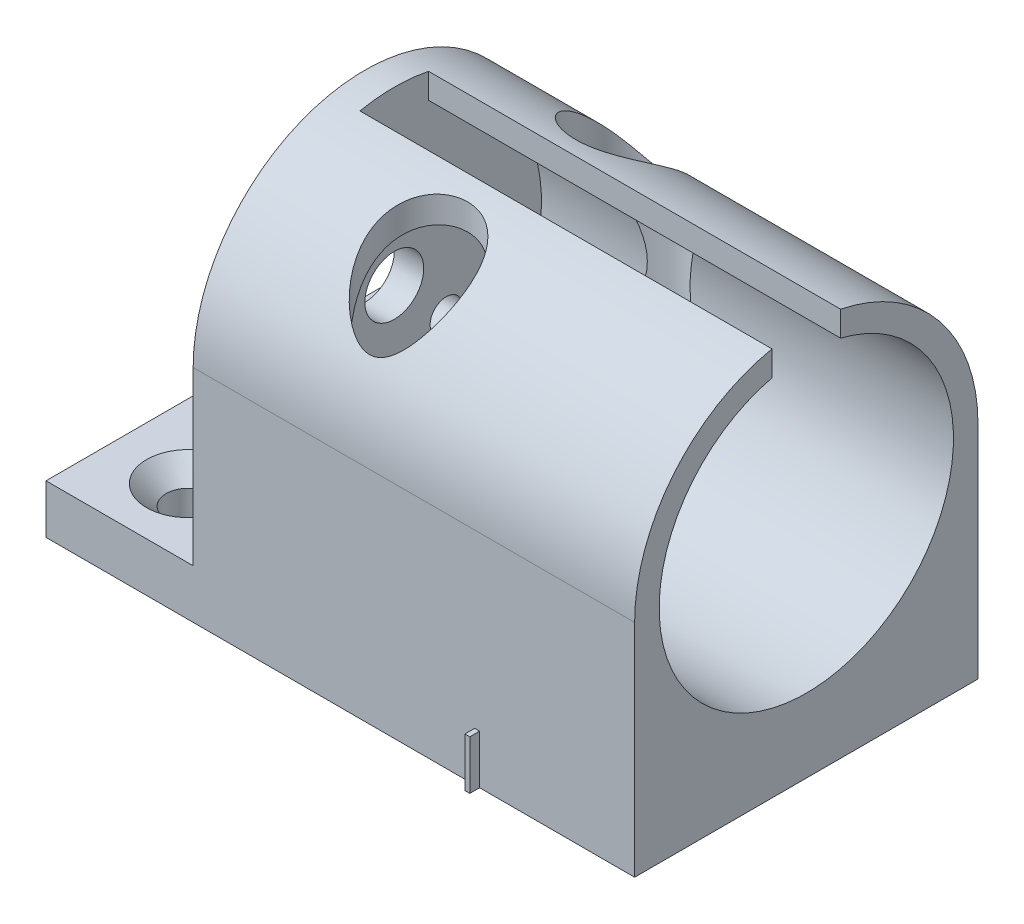
SolidWorks part; units mm, degrees
ref_plane "Front Plane" through (0, 0, 0) normal (0, 0, 1) x (1, 0, 0)
ref_plane "Top Plane" through (0, 0, 0) normal (0, 1, 0) x (1, 0, 0)
ref_plane "Right Plane" through (0, 0, 0) normal (1, 0, 0) x (0, 0, -1)
sketch "Sketch1" plane through (0, 0, 0) normal (0, 0, 1) x (1, 0, 0)
  line L0 (0.5, -17.5) -> (15.5, -17.5)
  line L1 (15.5, -17.5) -> (15.5, 17.5)
  line L2 (15.5, 17.5) -> (18.5, 17.5)
  line L3 (18.5, 17.5) -> (18.5, -17.5)
  line L4 (18.5, -17.5) -> (60.5, -17.5)
  line L5 (60.5, -17.5) -> (60.5, -22.5)
  line L9 (0.5, -22.5) -> (0.5, -17.5)
  line L10 (0.5, -22.5) -> (60.5, -22.5)
  line L15 (15, 5.6084) -> (15, -6.1785) construction
  point P0 (0, 0)
  point P14 (15.5, 0)
  dimension "D1" = 5
  dimension "D3" = 42
  dimension "D4" = 15
  dimension "D5" = 3
  dimension "D7" = 35
  dimension "D8" = 15
  dimension "D9" = 1
extrude "Boss-Extrude1" add sketch "Sketch1" along normal mid plane 35
sketch "Sketch2" plane through (0, 0, 17.5) normal (0, 0, 1) x (1, 0, 0)
  line L0 (60.5, -17.5) -> (18.5, -17.5) construction
  line L1 (44.2, -17.5) -> (44.7, -17.5)
  line L2 (44.2, -17.5) -> (44.2, -22.5)
  line L3 (44.2, -22.5) -> (44.7, -22.5)
  line L4 (44.7, -17.5) -> (44.7, -22.5)
  line L5 (0.5, -22.5) -> (60.5, -22.5) construction
  point P8 (44.45, -17.5)
  dimension "D1" = 44.45
  dimension "D2" = 0.5
extrude "Boss-Extrude2" add sketch "Sketch2" against normal offset from surface (37 mm away) 1 from offset 1 up to face at (23.75, -10, -17.5) offset beyond the face yes
sketch "Sketch3" plane through (15.5, 0, 0) normal (-1, 0, 0) x (0, 0, 1)
  line L0 (-5.3033, -5.3033) -> (5.3033, -5.3033) construction
  line L1 (-5.3033, -5.3033) -> (-5.3033, 5.3033) construction
  line L2 (5.3033, -5.3033) -> (5.3033, 5.3033) construction
  line L3 (-5.3033, 5.3033) -> (5.3033, 5.3033) construction
  line L4 (-5.3033, -5.3033) -> (5.3033, 5.3033) construction
  line L5 (5.3033, -5.3033) -> (-5.3033, 5.3033) construction
  circle A0 centre (0, 0) radius 3
  circle A1 centre (-5.3033, 5.3033) radius 1.65
  circle A2 centre (5.3033, 5.3033) radius 1.65
  circle A3 centre (5.3033, -5.3033) radius 1.65
  circle A4 centre (-5.3033, -5.3033) radius 1.65
  point P11 (7.5, 0)
  point P12 (4.7702, -5.7875)
  dimension "D2" = 6
  dimension "D3" = 3.3
  dimension "D1" = 15
extrude "Cut-Extrude1" cut sketch "Sketch3" against normal through all
sketch "Sketch4" plane through (18.5, 0, 0) normal (1, 0, 0) x (0, 0, -1)
  line L1 (-17.5, 17.5) -> (17.5, 17.5)
  line L2 (-17.5, 17.5) -> (-17.5, -17.5)
  line L3 (-17.5, -17.5) -> (17.5, -17.5)
  line L4 (17.5, 17.5) -> (17.5, -17.5)
  circle A0 centre (0, 0) radius 15
  dimension "D1" = 30
extrude "Boss-Extrude3" add sketch "Sketch4" along normal through all
sketch "Sketch5" plane through (60.5, 0, 0) normal (1, 0, 0) x (0, 0, -1)
  line L0 (-17.5, -22.5) -> (-17.5, 17.5) construction
  line L1 (-17.5, 0) -> (-17.5, 18.5)
  line L2 (-17.5, 18.5) -> (17.5, 18.5)
  line L3 (17.5, 18.5) -> (17.5, 0)
  line L4 (17.5, 17.5) -> (-17.5, 17.5) construction
  arc A0 (-17.5, 0) -> (17.5, 0) centre (0, 0) cw
  point P10 (0, 0)
  dimension "D1" = 1
extrude "Cut-Extrude2" cut sketch "Sketch5" against normal through all
sketch "Sketch6" plane through (0, -17.5, 0) normal (0, 1, 0) x (1, 0, 0)
  line L0 (31.475, -10.5) -> (31.475, 10.5) construction
  line L1 (15.5, -17.5) -> (60.5, -17.5) construction
  line L2 (44.45, 0) -> (18.5, 0) construction
  line L3 (44.7, -18.5) -> (44.2, -18.5) construction
  line L4 (18.5, -15) -> (18.5, 15) construction
  circle A0 centre (31.475, -10.5) radius 5
  circle A1 centre (31.475, 10.5) radius 5
  point P4 (31.475, 0)
  point P7 (31.475, -15.5)
  point P11 (0, 0)
  point P14 (44.45, -18.5)
  point P15 (31.475, 0)
  point P16 (0, 0)
  dimension "D1" = 10
  dimension "D2" = 2
extrude "Cut-Extrude3" cut sketch "Sketch6" along normal through all
sketch "Sketch7" plane through (0, -17.5, 0) normal (0, 1, 0) x (1, 0, 0)
  line L0 (15.5, 17.5) -> (0.5, 17.5) construction
  line L1 (8, 10.5) -> (31.475, 10.5) construction
  line L2 (8, 10.5) -> (8, -10.5) construction
  line L3 (8, -10.5) -> (31.475, -10.5) construction
  line L4 (31.475, 10.5) -> (31.475, -10.5) construction
  circle A1 centre (31.475, 10.5) radius 5 construction
  circle A2 centre (8, 10.5) radius 2.25
  circle A3 centre (8, -10.5) radius 2.25
  circle A4 centre (31.475, -10.5) radius 2.25
  circle A5 centre (31.475, 10.5) radius 2.25
  point P4 (8, 0)
  point P12 (8, 17.5)
  dimension "D1" = 4.5
extrude "Cut-Extrude4" cut sketch "Sketch7" against normal through all
chamfer "Chamfer1" distance 2 angle 45 4 edges at (8, -17.5, 12.75) (8, -17.5, -8.25) (31.475, -17.5, 12.75) (31.475, -17.5, -8.25)
sketch "Sketch8" plane through (60.5, 0, 0) normal (1, 0, 0) x (0, 0, -1)
  line L1 (-3.5, 14.586) -> (3.5, 14.586)
  line L2 (-3.5, 14.586) -> (-3.5, 17.5)
  line L3 (-3.5, 17.5) -> (3.5, 17.5)
  line L4 (3.5, 14.586) -> (3.5, 17.5)
  circle A0 centre (0, 0) radius 15 construction
  circle A1 centre (0, 0) radius 15 construction
  arc A2 (17.5, 0) -> (-17.5, 0) centre (0, 0) ccw construction
  point P6 (0, 0)
  dimension "D1" = 7
extrude "Cut-Extrude5" cut sketch "Sketch8" against normal up to surface (42 mm away) up to face at (18.5, 0, 3)
